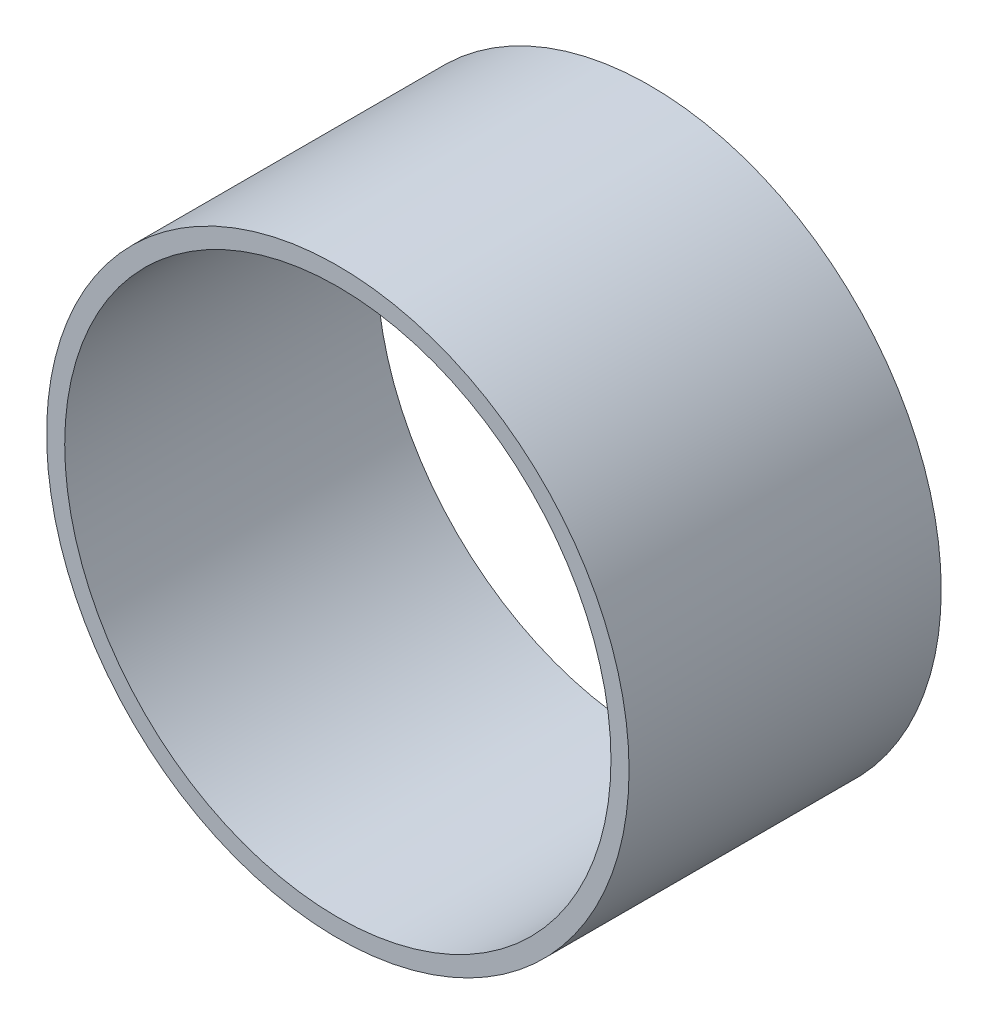
SolidWorks part; units mm, degrees
material "Hexcel AS4C (3000 Filaments)"
ref_plane "Front Plane" through (0, 0, 0) normal (0, 0, 1) x (1, 0, 0)
ref_plane "Top Plane" through (0, 0, 0) normal (0, 1, 0) x (1, 0, 0)
ref_plane "Right Plane" through (0, 0, 0) normal (1, 0, 0) x (0, 0, -1)
sketch "Sketch1" plane through (0, 0, 0) normal (0, 0, 1) x (1, 0, 0)
  circle A0 centre (0, 0) radius 23.6982
  circle A1 centre (0, 0) radius 22.225
  dimension "D1" = 47.3964
  dimension "D2" = 44.45
extrude "Boss-Extrude1" add sketch "Sketch1" along normal blind 25.4
